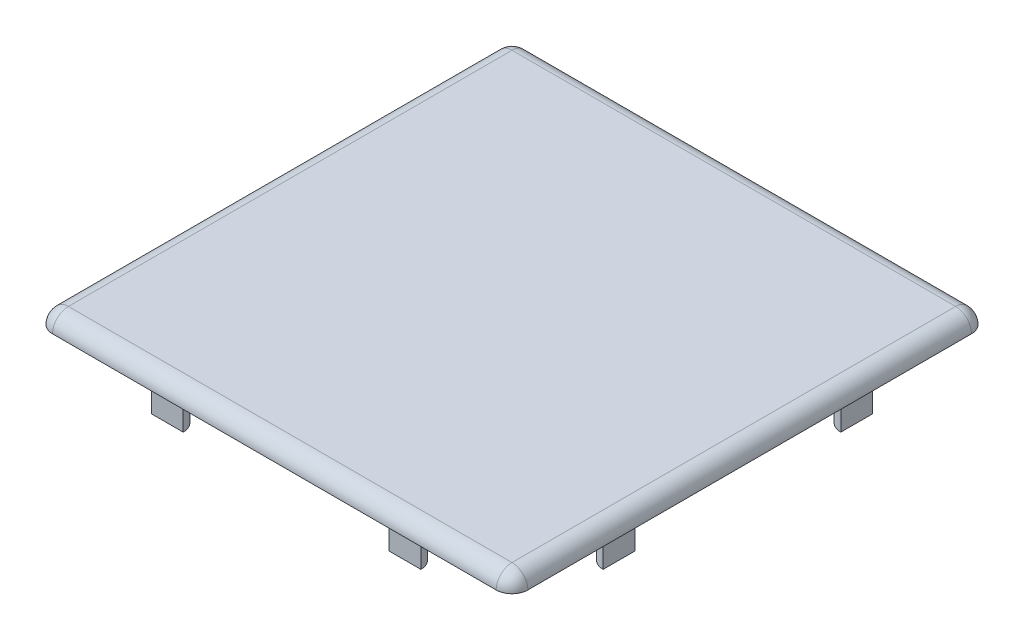
SolidWorks part; units mm, degrees
ref_plane "前视基准面" through (0, 0, 0) normal (0, 0, 1) x (1, 0, 0)
ref_plane "上视基准面" through (0, 0, 0) normal (0, 1, 0) x (1, 0, 0)
ref_plane "右视基准面" through (0, 0, 0) normal (1, 0, 0) x (0, 0, -1)
sketch "草图1" plane through (0, 0, 0) normal (0, 1, 0) x (1, 0, 0)
  line L0 (30, 30) -> (30, -30)
  line L1 (30, 30) -> (-30, 30)
  line L2 (30, -30) -> (-30, -30)
  line L3 (-30, 30) -> (-30, -30)
  line L4 (30, 30) -> (-30, -30) construction
  line L5 (30, -30) -> (-30, 30) construction
  point P1 (0, 0)
  dimension "D1" = 60
  dimension "D2" = 60
extrude "凸台-拉伸1" add sketch "草图1" along normal blind 2
sketch "草图2" plane through (0, 0, 0) normal (0, -1, 0) x (1, 0, 0)
  line L0 (-30, 30) -> (-28.5, 30) construction
  line L1 (-30, 30) -> (30, 30) construction
  line L2 (-28.5, 30) -> (-28.5, 15) construction
  line L3 (-28.5, 13) -> (-28.5, 17)
  arc A0 (-28.5, 13) -> (-28.5, 17) centre (-28.5, 15) ccw
  dimension "D3" = 4
  dimension "D1" = 1.5
  dimension "D2" = 15
extrude "凸台-拉伸2" add sketch "草图2" along normal blind 4
mirror "镜向1" about plane through (0, 0, 0) normal (0, 0, 1) of "凸台-拉伸2"
mirror "镜向2" about plane through (0, 0, 0) normal (1, 0, 0) of "镜向1", "凸台-拉伸2"
sketch "草图3" plane through (0, 0, 0) normal (0, -1, 0) x (1, 0, 0)
  line L0 (-30, 30) -> (-30, 28.5) construction
  line L1 (-30, -30) -> (-30, 30) construction
  line L2 (-30, 28.5) -> (-15, 28.5) construction
  line L3 (-13, 28.5) -> (-17, 28.5)
  arc A0 (-17, 28.5) -> (-13, 28.5) centre (-15, 28.5) ccw
  dimension "D3" = 4
  dimension "D1" = 1.5
  dimension "D2" = 15
extrude "凸台-拉伸3" add sketch "草图3" along normal blind 4
mirror "镜向3" about plane through (0, 0, 0) normal (1, 0, 0) of "凸台-拉伸3"
mirror "镜向4" about plane through (0, 0, 0) normal (0, 0, 1) of "镜向3", "凸台-拉伸3"
fillet "圆角1" radius 2 4 edges at (30, 2, 0) (0, 2, 30) (-30, 2, 0) (0, 2, -30)
